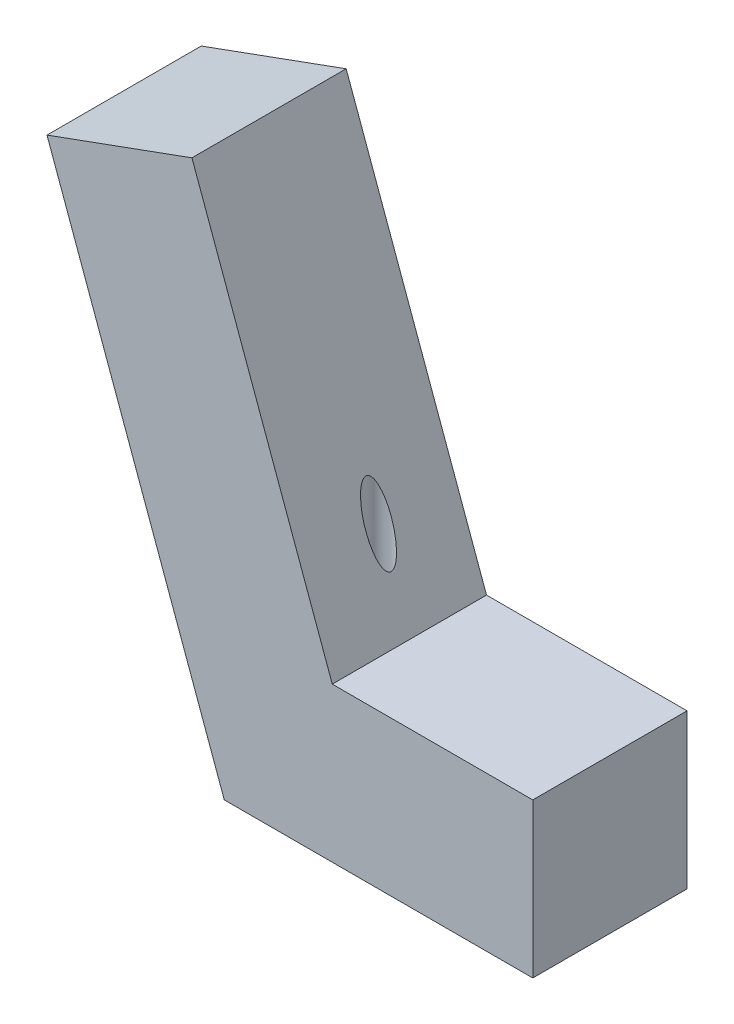
SolidWorks part; units mm, degrees
material "ABS"
ref_plane "Front Plane" through (0, 0, 0) normal (0, 0, 1) x (1, 0, 0)
ref_plane "Top Plane" through (0, 0, 0) normal (0, 1, 0) x (1, 0, 0)
ref_plane "Right Plane" through (0, 0, 0) normal (1, 0, 0) x (0, 0, -1)
sketch "Sketch1" plane through (0, 0, 0) normal (0, 0, 1) x (1, 0, 0)
  line L0 (0, 0) -> (-19.9502, 54.8127)
  line L1 (-19.9502, 54.8127) -> (3.918, 63.5)
  line L2 (3.918, 63.5) -> (27.0301, 0)
  line L3 (27.0301, 0) -> (60.0448, 0)
  line L4 (60.0448, 0) -> (60.0448, -25.4)
  line L5 (60.0448, -25.4) -> (9.2448, -25.4)
  line L6 (9.2448, -25.4) -> (0, 0)
  dimension "D1" = 25.4
  dimension "D2" = 70
  dimension "D3" = 88.9
  dimension "D4" = 50.8
extrude "Boss-Extrude1" add sketch "Sketch1" along normal blind 25.4
sketch "Sketch3" plane through (0, -25.4, 0) normal (0, -1, 0) x (1, 0, 0)
  line L0 (60.0448, 12.7) -> (9.2448, 12.7) construction
  line L1 (60.0448, 25.4) -> (60.0448, 0) construction
  line L2 (9.2448, 25.4) -> (9.2448, 0) construction
  circle A0 centre (21.9448, 12.7) radius 6.35
  dimension "D1" = 12.7
  dimension "D2" = 12.7
extrude "Cut-Extrude1" cut sketch "Sketch3" against normal blind 15.875
sketch "Sketch4" plane through (0, -9.525, 0) normal (0, -1, 0) x (1, 0, 0)
  circle A0 centre (21.9448, 12.7) radius 6.35 construction
  circle A1 centre (21.9448, 12.7) radius 6.35 construction
  circle A2 centre (21.9448, 12.7) radius 2.0955
  dimension "D1" = 4.191
extrude "Cut-Extrude2" cut sketch "Sketch4" against normal through all
